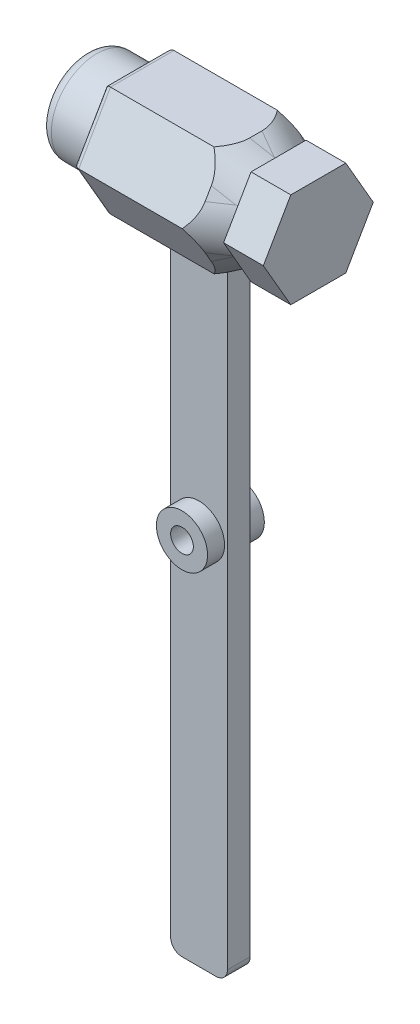
SolidWorks part; units mm, degrees
ref_plane "Front Plane" through (0, 0, 0) normal (0, 0, 1) x (1, 0, 0)
ref_plane "Top Plane" through (0, 0, 0) normal (0, 1, 0) x (1, 0, 0)
ref_plane "Right Plane" through (0, 0, 0) normal (1, 0, 0) x (0, 0, -1)
sketch "Sketch1" plane through (0, 0, 0) normal (0, 0, 1) x (1, 0, 0)
  line L0 (0, 110.5) -> (10, 110.5)
  line L1 (2, 0) -> (8, 0)
  line L2 (0, 2) -> (0, 130)
  line L3 (0, 130) -> (10, 130)
  line L4 (10, 2) -> (10, 130)
  circle A0 centre (5, 66.5) radius 4.5
  circle A1 centre (5, 66.5) radius 2
  arc A2 (0, 2) -> (2, 0) centre (2, 2) ccw
  arc A3 (8, 0) -> (10, 2) centre (8, 2) ccw
  point P12 (0, 0)
  point P15 (10, 0)
  dimension "D5" = 9
  dimension "D6" = 4
  dimension "D8" = 2
  dimension "D1" = 10
  dimension "D2" = 130
  dimension "D3" = 66.5
  dimension "D4" = 5
  dimension "D7" = 44
sketch "Sketch2" plane through (0, 0, 0) normal (1, 0, 0) x (0, 0, -1)
  line L0 (0, 130) -> (0, 110.4044) construction
  line L1 (0, 2) -> (0, 130) construction
  line L3 (-11.1751, 120.2022) -> (-5.5875, 110.5243)
  line L4 (-5.5875, 110.5243) -> (5.5875, 110.5243)
  line L5 (5.5875, 110.5243) -> (11.1751, 120.2022)
  line L6 (11.1751, 120.2022) -> (5.5875, 129.8801)
  line L7 (5.5875, 129.8801) -> (-5.5875, 129.8801)
  line L8 (-5.5875, 129.8801) -> (-11.1751, 120.2022)
  line L9 (9.6779, 120.2022) -> (4.839, 128.5835)
  line L10 (4.839, 128.5835) -> (-4.839, 128.5835)
  line L11 (-4.839, 128.5835) -> (-9.6779, 120.2022)
  line L12 (-9.6779, 120.2022) -> (-4.839, 111.8209)
  line L13 (-4.839, 111.8209) -> (4.839, 111.8209)
  line L14 (4.839, 111.8209) -> (9.6779, 120.2022)
  circle A0 centre (0, 120.2022) radius 8
  circle A1 centre (0, 120.2022) radius 9.6779 construction
  circle A2 centre (0, 120.2022) radius 8.3813 construction
extrude "Boss-Extrude1" add sketch "Sketch1" along normal mid plane 4 contours L1 A3 L4 L0 L2 A2 A0 | A0 A1 region at (5, 54.6521, 0) region at (0.6273, 66.5, 0)
extrude "Boss-Extrude2" add sketch "Sketch1<3>" along normal mid plane 10 contours A0 A1 region at (0.6273, 66.5, 0)
sketch "Sketch1<3>" plane through (0, 0, 0) normal (0, 0, 1) x (1, 0, 0) same geometry as "Sketch1"
extrude "Boss-Extrude3" add sketch "Sketch2" against normal blind 17 separate body contours A0 region at (0, 120.2022, 0)
extrude "Boss-Extrude5" add sketch "Sketch2<4>" along normal blind 20 and the other way blind 8 contours A0 | L7 L8 L3 L4 L5 L6 A0 | L13 L14 L9 L10 L11 L12 A0 region at (0, 124.8933, 8.1253) region at (0, 116.1395, -7.0367) region at (0, 120.2022, 0)
sketch "Sketch2<4>" plane through (0, 0, 0) normal (1, 0, 0) x (0, 0, -1) same geometry as "Sketch2"
fillet "Fillet3" radius 1 6 edges at (-8, 129.8801, 0) (-8, 125.0411, -8.3813) (-8, 115.3632, -8.3813) (-8, 110.5243, 0) (-8, 115.3632, 8.3813) (-8, 125.0411, 8.3813)
fillet "Fillet4" radius 2 1 edges at (-17, 120.2022, -8)
chamfer "Chamfer1" distance 7 angle 30 6 edges at (20, 125.0411, -8.3813) (20, 115.3632, -8.3813) (20, 110.5243, 0) (20, 115.3632, 8.3813) (20, 125.0411, 8.3813) (20, 129.8801, 0) first distance on face at (6.5, 125.0411, -8.3813) first distance on face at (6.5, 115.3632, -8.3813) first distance on face at (6.5, 110.5243, 0) first distance on face at (6.5, 115.3632, 8.3813) first distance on face at (6.5, 125.0411, 8.3813) first distance on face at (6.5, 129.8801, 0)
fillet "Fillet5" radius 9 6 edges at (16.5, 120.2022, 8.8418) (16.5, 112.545, 4.4209) (16.5, 112.545, -4.4209) (16.5, 120.2022, -8.8418) (16.5, 127.8594, -4.4209) (16.5, 127.8594, 4.4209)
extrude "Boss-Extrude6" add sketch "Sketch2<7>" along normal blind 4 and the other way blind 3 from offset 20 contours A0 | L13 L14 L9 L10 L11 L12 A0 region at (0, 116.1395, -7.0367) region at (0, 120.2022, 0)
sketch "Sketch2<7>" plane through (0, 0, 0) normal (1, 0, 0) x (0, 0, -1) same geometry as "Sketch2"
